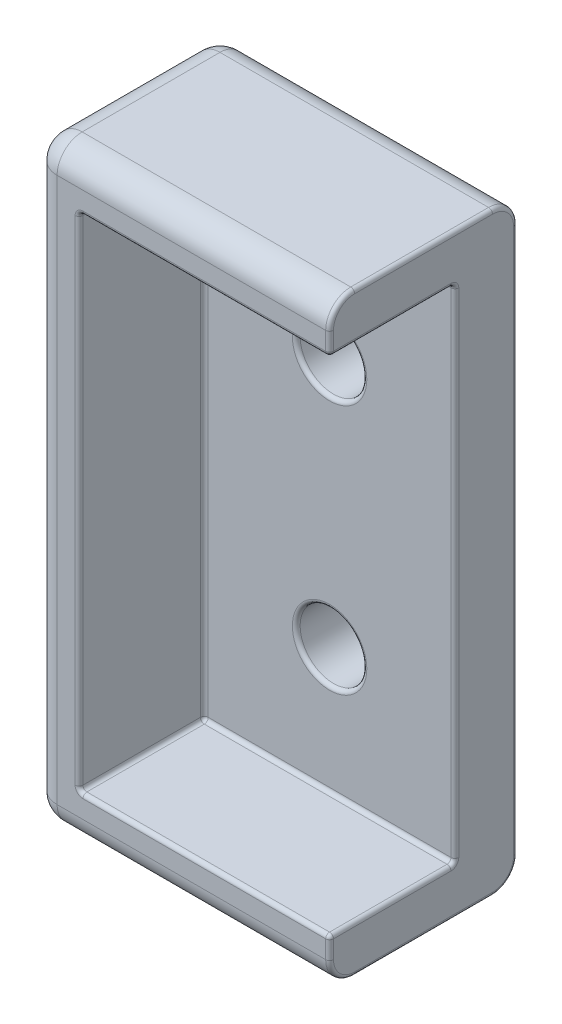
SolidWorks part; units mm, degrees
material "Choose your Material"
ref_plane "Front Plane" through (0, 0, 0) normal (0, 0, 1) x (1, 0, 0)
ref_plane "Top Plane" through (0, 0, 0) normal (0, 1, 0) x (1, 0, 0)
ref_plane "Right Plane" through (0, 0, 0) normal (1, 0, 0) x (0, 0, -1)
sketch "Sketch1" plane through (0, 0, 0) normal (0, 0, 1) x (1, 0, 0)
  line L0 (0, 25.4) -> (-25.4, 25.4)
  line L1 (0, 30.1625) -> (-30.1625, 30.1625)
  line L2 (0, 30.1625) -> (0, -30.1625)
  line L3 (0, -30.1625) -> (-30.1625, -30.1625)
  line L4 (-30.1625, 30.1625) -> (-30.1625, -30.1625)
  line L5 (-25.4, 25.4) -> (-25.4, -25.4)
  line L6 (-25.4, -25.4) -> (0, -25.4)
  line L7 (0, 0) -> (-25.4, 0) construction
  dimension "D1" = 50.8
  dimension "D2" = 25.4
  dimension "D3" = 4.7625
  dimension "D4" = 4.7625
extrude "Boss-Extrude1" add sketch "Sketch1" against normal blind 19.05 contours L6 L5 L0 L2 L1 L4 L3 | L7 L2 L0 L5 | L2 L7 L5 L6 region at (-12.7, 12.7, 0) region at (-12.7, 26.0745, 0) region at (-12.7, -12.7, 0)
extrude "Cut-Extrude1" cut sketch "Sketch1<3>" against normal blind 12.7 contours L7 L2 L0 L5 | L2 L7 L5 L6 region at (-12.7, 12.7, 0) region at (-12.7, -12.7, 0)
sketch "Sketch1<3>" plane through (0, 0, 0) normal (0, 0, 1) x (1, 0, 0) same geometry as "Sketch1"
sketch "Sketch3" plane through (0, 0, -12.7) normal (0, 0, 1) x (1, 0, 0)
  line L0 (-25.4, 25.4) -> (-12.7, 12.7) construction
  line L1 (-12.7, 12.7) -> (0, 25.4) construction
  line L2 (-25.4, -25.4) -> (-12.7, -12.7) construction
  line L3 (-12.7, -12.7) -> (0, -25.4) construction
  line L4 (-12.7, -12.7) -> (-12.7, 12.7) construction
  circle A0 centre (-12.7, -12.7) radius 3 construction
  circle A1 centre (-12.7, 12.7) radius 3 construction
  dimension "D1" = 6
  dimension "D2" = 25.4
hole_wizard "1/4 Clearance Hole1" positions "Sketch4" profile "Sketch5" hole size "1/4" standard "ANSI Inch"
sketch "Sketch4" plane through (0, 0, -12.7) normal (0, 0, 1) x (1, 0, 0)
  point P0 (-12.7, 12.7)
  point P3 (-12.7, -12.7)
sketch "Sketch5" plane through (-12.7, 12.7, -12.7) normal (1, 0, 0) x (0, -1, 0)
  line L0 (0, 0) -> (0, 32.0272)
  line L1 (0, 32.0272) -> (3.3782, 29.9974)
  line L2 (3.3782, 29.9974) -> (3.3782, 0)
  line L5 (3.3782, 0) -> (0, 0)
  line L10 (0, 32.0272) -> (-3.3782, 29.9974) construction
  line L11 (0, -6.35) -> (0, 107.95) construction
  dimension "Hole Dia." = 6.7564
  dimension "Hole Depth" = 29.9974
  dimension "Drill Angle" = 118
fillet "Fillet1" radius 2.54 8 edges at (-30.1625, 0, 0) (-15.0812, 30.1625, 0) (-15.0812, -30.1625, 0) (-15.0812, -30.1625, -19.05) (-30.1625, -30.1625, -9.525) (-30.1625, 30.1625, -9.525) (-15.0812, 30.1625, -19.05) (-30.1625, 0, -19.05)
fillet "Fillet2" radius 0.3969 24 edges at (-12.7, 25.4, 0) (-12.7, -25.4, 0) (0, 29.4186, -18.3061) (0, 0, -19.05) (0, -29.4186, -18.3061) (0, -30.1625, -9.525) (0, -29.4186, -0.7439) (0, -26.5113, 0) (0, -25.4, -6.35) (0, 25.4, -6.35) (0, 26.5113, 0) (0, 29.4186, -0.7439) (0, 30.1625, -9.525) (-12.7, 25.4, -12.7) (0, 0, -12.7) (-12.7, -25.4, -12.7) (-25.4, 25.4, -6.35) (-25.4, 0, -12.7) (-25.4, -25.4, -6.35) (-25.4, 0, 0) (-9.3218, -12.7, -12.7) (-9.3218, 12.7, -12.7) (-9.3218, -12.7, -19.05) (-9.3218, 12.7, -19.05)
